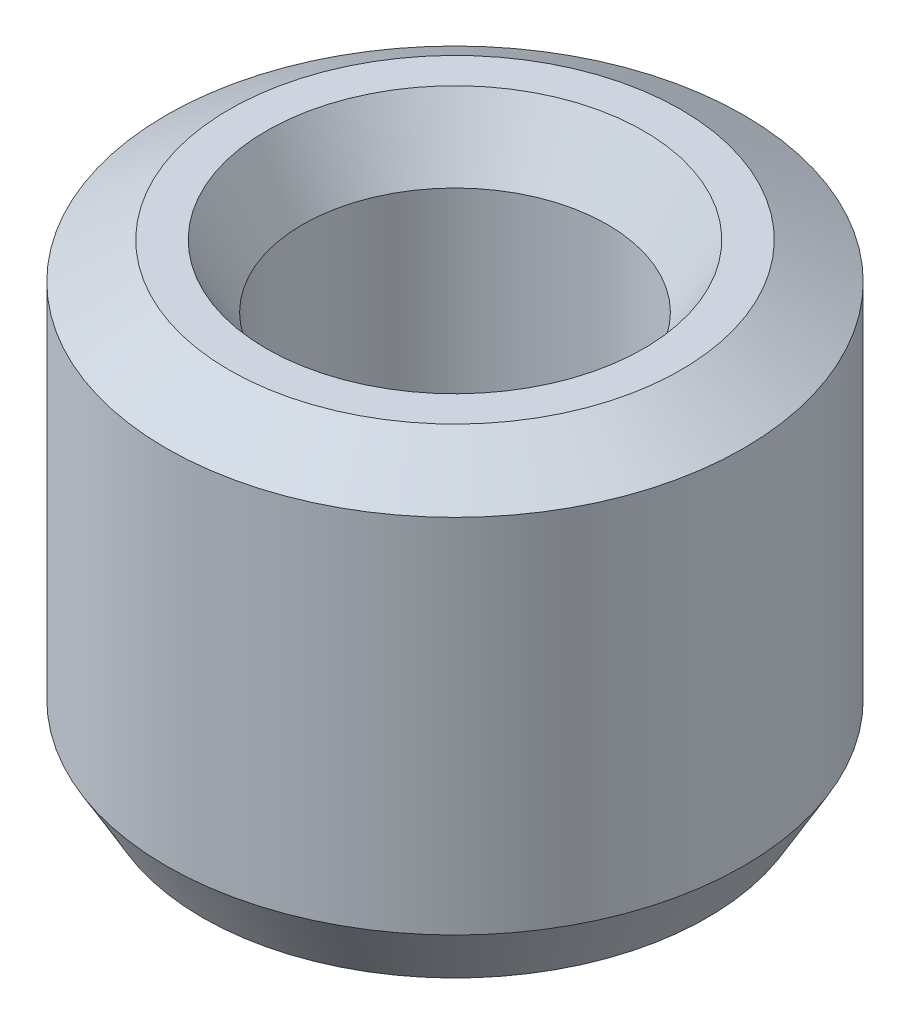
SolidWorks part; units mm, degrees
ref_plane "Front Plane" through (0, 0, 0) normal (0, 0, 1) x (1, 0, 0)
ref_plane "Top Plane" through (0, 0, 0) normal (0, 1, 0) x (1, 0, 0)
ref_plane "Right Plane" through (0, 0, 0) normal (1, 0, 0) x (0, 0, -1)
sketch "Sketch1" plane through (0, 0, 0) normal (0, 1, 0) x (1, 0, 0)
  circle A0 centre (0, 0) radius 27.5
  dimension "SLEEVE_OD" = 55
extrude "Boss-Extrude1" add sketch "Sketch1" along normal blind 43.9122
sketch "Sketch2" plane through (0, 0, 0) normal (0, 1, 0) x (1, 0, 0)
  circle A0 centre (0, 0) radius 14.5131
  dimension "BORE_D" = 29.0261
extrude "Cut-Extrude1" cut sketch "Sketch2" along normal through all
chamfer "Chamfer1" distance 3.4595 angle 60 4 edges at (0, 43.9122, 14.5131) (0, 0, 14.5131) (0, 0, 27.5) (0, 43.9122, 27.5) first distance on face at (0, 43.9122, 14.5131) first distance on face at (0, 0, 14.5131) first distance on face at (0, 43.9122, 27.5)
